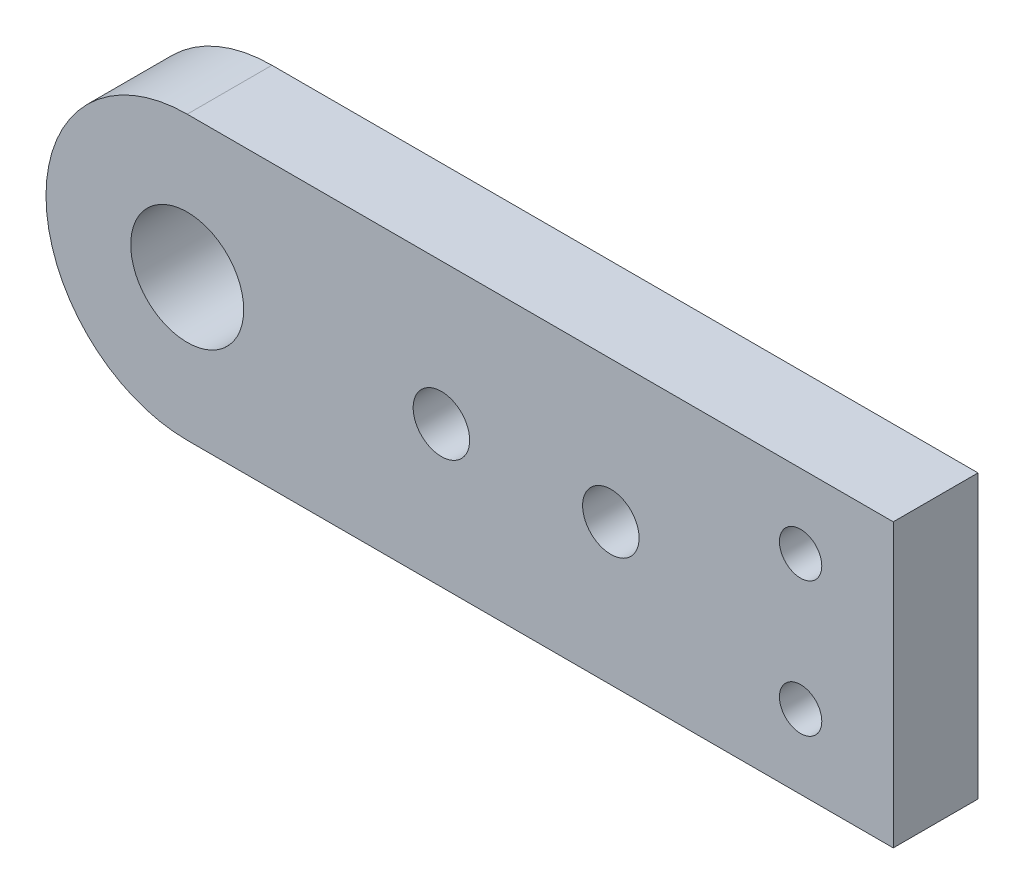
SolidWorks part; units mm, degrees
ref_plane "Plano frontal" through (0, 0, 0) normal (0, 0, 1) x (1, 0, 0)
ref_plane "Plano superior" through (0, 0, 0) normal (0, 1, 0) x (1, 0, 0)
ref_plane "Plano direito" through (0, 0, 0) normal (1, 0, 0) x (0, 0, -1)
sketch "Esboço1" plane through (0, 0, 0) normal (0, 0, 1) x (1, 0, 0)
  line L0 (-30, 0) -> (-20, 0) construction
  line L1 (-30, 10) -> (30, 10)
  line L2 (-30, 10) -> (-30, -10)
  line L3 (-30, -10) -> (30, -10)
  line L4 (30, 10) -> (30, -10)
  line L5 (-30, 10) -> (30, -10) construction
  line L6 (-30, -10) -> (30, 10) construction
  line L7 (30, 0) -> (10, 0) construction
  line L8 (10, 0) -> (-2, 0) construction
  circle A0 centre (-20, 0) radius 4
  circle A1 centre (10, 0) radius 2
  circle A2 centre (-2, 0) radius 2
  point P0 (0, 0)
  dimension "D4" = 8
  dimension "D5" = 4
  dimension "D1" = 20
  dimension "D2" = 60
  dimension "D3" = 10
  dimension "D6" = 20
  dimension "D7" = 12
extrude "Ressalto-extrusão1" add sketch "Esboço1" along normal blind 6
fillet "Filete1" radius 10 2 edges at (-30, -10, 3) (-30, 10, 3)
ref_plane "Plano1" through (0, 0, 0) normal (0, 1, 0) x (1, 0, 0)
sketch "Esboço2" plane through (0, 0, 6) normal (0, 0, 1) x (1, 0, 0)
  circle A0 centre (23.4375, -4.7625) radius 1.175 construction
  circle A1 centre (23.4375, 4.7625) radius 1.175 construction
  circle A2 centre (23.4375, -4.7625) radius 1.175 construction
  circle A3 centre (23.4375, 4.7625) radius 1.175 construction
  circle A4 centre (23.4375, 4.7625) radius 1.5
  circle A5 centre (23.4375, -4.7625) radius 1.5
  dimension "D1" = 3
extrude "Corte-extrusão1" cut sketch "Esboço2" against normal up to surface (6 mm away) up to face at (-2.8284, 0, 0)
sketch "Esboço3" plane through (0, 0, 0) normal (0, 0, -1) x (-1, 0, 0)
  circle A0 centre (-23.4375, 4.7625) radius 2.5
  circle A1 centre (-23.4375, -4.7625) radius 2.5
  dimension "D1" = 5
extrude "Corte-extrusão2" cut sketch "Esboço3" against normal blind 2.4
